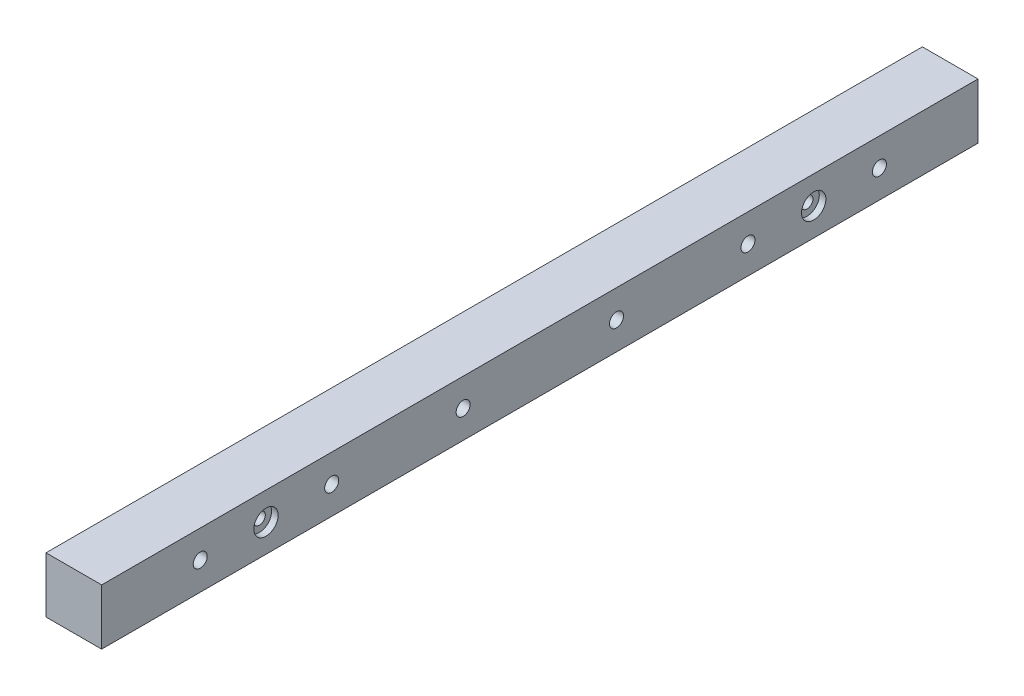
SolidWorks part; units mm, degrees
material "Delrin 2700 NC010, Low Viscosity Acetal Copolymer (SS)"
ref_plane "Front Plane" through (0, 0, 0) normal (0, 0, 1) x (1, 0, 0)
ref_plane "Top Plane" through (0, 0, 0) normal (0, 1, 0) x (1, 0, 0)
ref_plane "Right Plane" through (0, 0, 0) normal (1, 0, 0) x (0, 0, -1)
sketch "Sketch1" plane through (0, 0, 0) normal (0, 0, 1) x (1, 0, 0)
  line L0 (0, 0) -> (0, 25.6877) construction
  line L1 (12.7, -12.7) -> (-12.7, -12.7)
  line L2 (12.7, -12.7) -> (12.7, 12.7)
  line L3 (12.7, 12.7) -> (-12.7, 12.7)
  line L4 (-12.7, -12.7) -> (-12.7, 12.7)
  line L5 (0, 0) -> (36.1991, 0) construction
  dimension "D1" = 25.4
  dimension "D2" = 25.4
extrude "Boss-Extrude1" add sketch "Sketch1" along normal blind 200 and the other way blind 200
sketch "Sketch5" plane through (12.7, 0, 0) normal (1, 0, 0) x (0, 0, -1)
  circle A0 centre (-155, 0) radius 3.2
  circle A1 centre (-95, 0) radius 3.2
  circle A2 centre (-35, 0) radius 3.2
  circle A3 centre (35, 0) radius 3.2
  circle A4 centre (95, 0) radius 3.2
  circle A5 centre (155, 0) radius 3.2
  circle A6 centre (155, 0) radius 3.2 construction
  circle A7 centre (95, 0) radius 3.2 construction
  circle A8 centre (35, 0) radius 3.2 construction
  circle A9 centre (-35, 0) radius 3.2 construction
  circle A10 centre (-95, 0) radius 3.2 construction
  circle A11 centre (-155, 0) radius 3.2 construction
extrude "Cut-Extrude1" cut sketch "Sketch5" against normal through all
sketch "Sketch6" plane through (-12.7, 0, 0) normal (-1, 0, 0) x (0, 0, 1)
  circle A0 centre (-155, 0) radius 4
  circle A1 centre (-95, 0) radius 4
  circle A2 centre (-35, 0) radius 4
  circle A3 centre (35, 0) radius 4
  circle A4 centre (95, 0) radius 4
  circle A5 centre (155, 0) radius 4
  circle A6 centre (-155, 0) radius 3.2 construction
  circle A7 centre (-95, 0) radius 3.2 construction
  circle A8 centre (-35, 0) radius 3.2 construction
  circle A9 centre (35, 0) radius 3.2 construction
  circle A10 centre (95, 0) radius 3.2 construction
  circle A11 centre (155, 0) radius 3.2 construction
  dimension "D1" = 8
extrude "Cut-Extrude2" cut sketch "Sketch6" against normal blind 3
sketch "Sketch7" plane through (0, 0, 0) normal (0, 1, 0) x (1, 0, 0)
  line L0 (12.7, 125) -> (-53.8772, 125) construction
  line L1 (12.7, -125) -> (-53.8772, -125) construction
  line L2 (0, 0) -> (-85.0635, 0) construction
  line L3 (-12.7, 125) -> (-12.7, 119)
  line L4 (-12.7, 119) -> (2.3, 119)
  line L5 (2.3, 119) -> (4.2053, 122.3)
  line L6 (-12.7, 125) -> (12.7, 125)
  line L7 (12.7, 212.738) -> (12.7, -210.6836) construction
  line L8 (12.7, 119.4437) -> (12.7, 125)
  line L9 (-12.7, 200) -> (-12.7, -200) construction
  line L10 (12.7, 119.4437) -> (9.7, 119.4437)
  line L11 (9.7, 119.4437) -> (9.7, 122.3)
  line L12 (9.7, 122.3) -> (4.2053, 122.3)
  dimension "D1" = 12
  dimension "D2" = 60
  dimension "D3" = 5.4
  dimension "D4" = 3
  dimension "D5" = 11.1125
  dimension "D6" = 15
revolve "Cut-Revolve1" cut sketch "Sketch7" angle 360 about L0
mirror "Mirror1" about plane through (0, 0, 0) normal (0, 0, 1) of "Cut-Revolve1"
